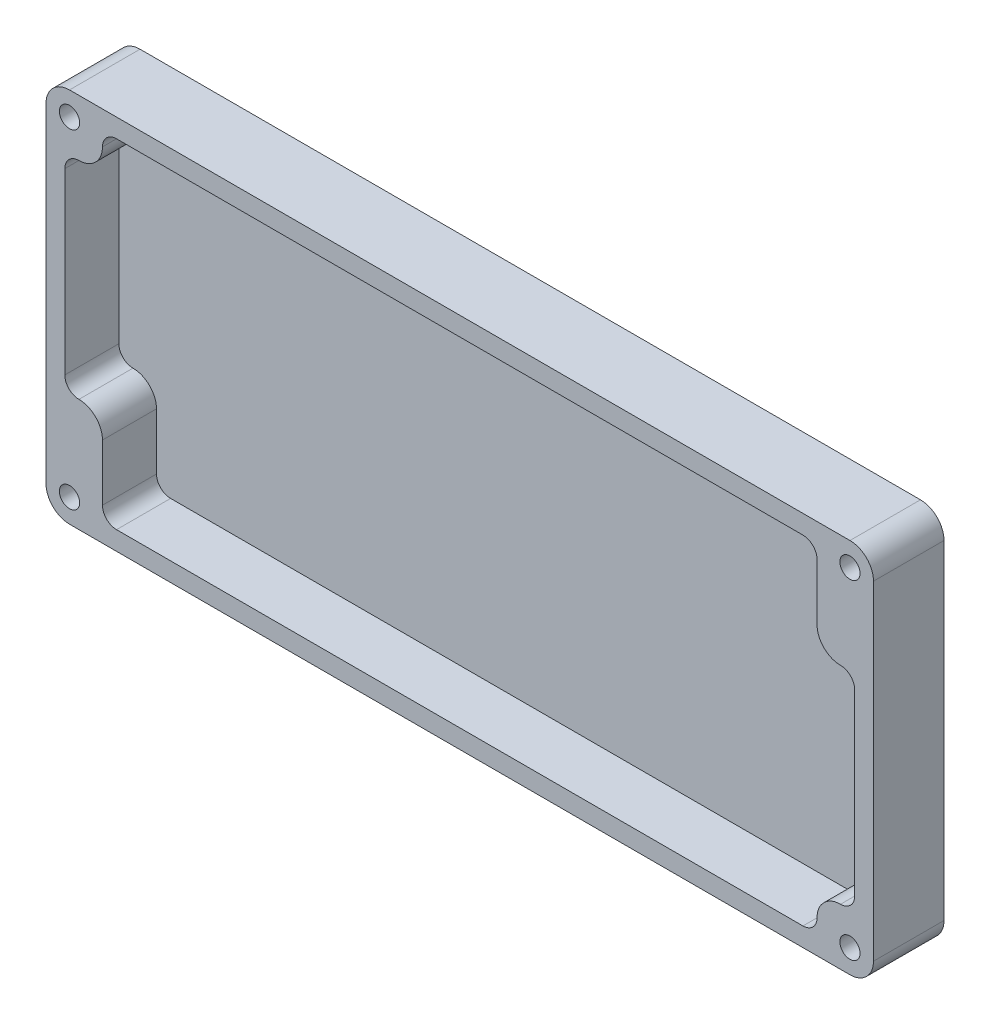
SolidWorks part; units mm, degrees
material "ألمنيوم خلائطي"
ref_plane "Front" through (0, 0, 0) normal (0, 0, 1) x (1, 0, 0)
ref_plane "Top" through (0, 0, 0) normal (0, 1, 0) x (1, 0, 0)
ref_plane "Right" through (0, 0, 0) normal (1, 0, 0) x (0, 0, -1)
sketch "Sketch1" plane through (0, 0, 0) normal (0, 0, 1) x (1, 0, 0)
  line L0 (88, 40) -> (-88, -40) construction
  line L1 (-88, 40) -> (88, 40)
  line L2 (-88, 40) -> (-88, -40)
  line L3 (-88, -40) -> (88, -40)
  line L4 (88, 40) -> (88, -40)
  dimension "D1" = 176
  dimension "D2" = 80
extrude "Boss-Extrude1" add sketch "Sketch1" along normal blind 38.5
sketch "Sketch2" plane through (0, 0, 38.5) normal (0, 0, 1) x (1, 0, 0)
  line L8 (-84, 36) -> (-84, -36)
  line L9 (-84, -36) -> (84, -36)
  line L10 (84, -36) -> (84, 36)
  line L11 (84, 36) -> (-84, 36)
  line L12 (-84, 36) -> (-84, -36)
  line L13 (-84, -36) -> (84, -36)
  line L14 (84, -36) -> (84, 36)
  line L15 (84, 36) -> (-84, 36)
  dimension "D1" = 4
extrude "Cut-Extrude1" cut sketch "Sketch2" against normal blind 35
fillet "Fillet2" radius 5 4 edges at (88, 40, 19.25) (88, -40, 19.25) (-88, -40, 19.25) (-88, 40, 19.25)
sketch "Sketch8" plane through (0, 0, 3.5) normal (0, 0, 1) x (1, 0, 0)
  line L0 (84, 36) -> (-84, 36) construction
  line L1 (76, 36) -> (84, 36)
  line L2 (76, 36) -> (76, 16)
  line L3 (76, 16) -> (84, 16)
  line L4 (84, 36) -> (84, 16)
  line L5 (84, -36) -> (84, 36) construction
  line L6 (-84, -36) -> (84, -36) construction
  line L7 (84, -28) -> (76, -28)
  line L8 (84, -28) -> (84, -36)
  line L9 (84, -36) -> (76, -36)
  line L10 (76, -28) -> (76, -36)
  line L11 (-84, 36) -> (-84, -36) construction
  line L12 (-76, -36) -> (-84, -36)
  line L13 (-76, -36) -> (-76, -16)
  line L14 (-76, -16) -> (-84, -16)
  line L15 (-84, -36) -> (-84, -16)
  line L16 (88, -35) -> (88, 35) construction
  line L17 (-84, 28) -> (-76, 28)
  line L18 (-84, 28) -> (-84, 36)
  line L19 (-84, 36) -> (-76, 36)
  line L20 (-76, 28) -> (-76, 36)
  dimension "D1" = 12
  dimension "D2" = 20
extrude "Boss-Extrude2" add sketch "Sketch8" along normal up to surface (35 mm away) up to face at (0, 0, 38.5)
fillet "Fillet4" radius 3 8 edges at (-76, 36, 21) (84, -28, 21) (76, -36, 21) (-76, -36, 21) (-84, -16, 21) (-84, 28, 21) (84, 16, 21) (76, 36, 21)
fillet "Fillet5" radius 5 4 edges at (-76, -16, 21) (76, -28, 21) (76, 16, 21) (-76, 28, 21)
hole_wizard "M4 Tapped Hole1" positions "Sketch5" profile "Sketch4" tap size "M4" standard "ISO"
sketch "Sketch5" plane through (0, 0, 38.5) normal (0, 0, 1) x (1, 0, 0)
  line L0 (-83, 35) -> (83, 35) construction
  line L1 (83, 35) -> (83, -35) construction
  line L2 (83, -35) -> (-83, -35) construction
  line L3 (-83, -35) -> (-83, 35) construction
  line L5 (-83, -35) -> (83, 35) construction
  line L7 (88, -35) -> (88, 35) construction
  line L8 (83, 40) -> (-83, 40) construction
  point P1 (-83, -35)
  point P5 (83, 35)
  point P33 (-83, 35)
  point P35 (83, -35)
  dimension "D1" = 5
  dimension "D2" = 5
sketch "Sketch4" plane through (-83, -35, 38.5) normal (1, 0, 0) x (0, -1, 0)
  line L0 (0, 0) -> (0, 12.4914)
  line L1 (0, 12.4914) -> (1.65, 11.5)
  line L2 (1.65, 11.5) -> (1.65, 0)
  line L5 (1.65, 0) -> (0, 0)
  line L10 (0, 12.4914) -> (-1.65, 11.5) construction
  line L11 (0, -6.35) -> (0, 107.95) construction
  dimension "Tap Drill Dia." = 3.3
  dimension "Tap Drill Depth" = 11.5
  dimension "Drill Angle" = 118
cosmetic thread "Hole Thread1" parameters "D1"=8, "D2"=4
cosmetic thread "Hole Thread2" parameters "D1"=8, "D2"=4
cosmetic thread "Hole Thread3" parameters "D1"=8, "D2"=4
cosmetic thread "Hole Thread4" parameters "D1"=8, "D2"=4
sketch "Sketch9" plane through (0, 0, 38.5) normal (0, 0, 1) x (1, 0, 0)
  line L0 (73, 37.5) -> (-73, 37.5)
  line L1 (-85.5, 25) -> (-85.5, -13)
  line L2 (-77.5, -21) -> (-77.5, -33)
  line L3 (-73, -37.5) -> (73, -37.5)
  line L4 (85.5, -25) -> (85.5, 13)
  line L5 (77.5, 21) -> (77.5, 33)
  line L6 (73, 36) -> (-73, 36)
  line L7 (-84, 25) -> (-84, -13)
  line L8 (-76, -21) -> (-76, -33)
  line L9 (-73, -36) -> (73, -36)
  line L10 (84, -25) -> (84, 13)
  line L11 (76, 21) -> (76, 33)
  line L12 (73, 36) -> (-73, 36)
  line L13 (-84, 25) -> (-84, -13)
  line L14 (-76, -21) -> (-76, -33)
  line L15 (-73, -36) -> (73, -36)
  line L16 (84, -25) -> (84, 13)
  line L17 (76, 21) -> (76, 33)
  arc A0 (-73, 37.5) -> (-77.5, 33) centre (-73, 33) ccw
  arc A1 (-81, 29.5) -> (-77.5, 33) centre (-81, 33) ccw
  arc A2 (-81, 29.5) -> (-85.5, 25) centre (-81, 25) ccw
  arc A3 (-85.5, -13) -> (-81, -17.5) centre (-81, -13) ccw
  arc A4 (-77.5, -21) -> (-81, -17.5) centre (-81, -21) ccw
  arc A5 (-77.5, -33) -> (-73, -37.5) centre (-73, -33) ccw
  arc A6 (73, -37.5) -> (77.5, -33) centre (73, -33) ccw
  arc A7 (81, -29.5) -> (77.5, -33) centre (81, -33) ccw
  arc A8 (81, -29.5) -> (85.5, -25) centre (81, -25) ccw
  arc A9 (85.5, 13) -> (81, 17.5) centre (81, 13) ccw
  arc A10 (77.5, 21) -> (81, 17.5) centre (81, 21) ccw
  arc A11 (77.5, 33) -> (73, 37.5) centre (73, 33) ccw
  arc A12 (-73, 36) -> (-76, 33) centre (-73, 33) ccw
  arc A13 (-81, 28) -> (-76, 33) centre (-81, 33) ccw
  arc A14 (-81, 28) -> (-84, 25) centre (-81, 25) ccw
  arc A15 (-84, -13) -> (-81, -16) centre (-81, -13) ccw
  arc A16 (-76, -21) -> (-81, -16) centre (-81, -21) ccw
  arc A17 (-76, -33) -> (-73, -36) centre (-73, -33) ccw
  arc A18 (73, -36) -> (76, -33) centre (73, -33) ccw
  arc A19 (81, -28) -> (76, -33) centre (81, -33) ccw
  arc A20 (81, -28) -> (84, -25) centre (81, -25) ccw
  arc A21 (84, 13) -> (81, 16) centre (81, 13) ccw
  arc A22 (76, 21) -> (81, 16) centre (81, 21) ccw
  arc A23 (76, 33) -> (73, 36) centre (73, 33) ccw
  arc A24 (-73, 36) -> (-76, 33) centre (-73, 33) ccw
  arc A25 (-81, 28) -> (-76, 33) centre (-81, 33) ccw
  arc A26 (-81, 28) -> (-84, 25) centre (-81, 25) ccw
  arc A27 (-84, -13) -> (-81, -16) centre (-81, -13) ccw
  arc A28 (-76, -21) -> (-81, -16) centre (-81, -21) ccw
  arc A29 (-76, -33) -> (-73, -36) centre (-73, -33) ccw
  arc A30 (73, -36) -> (76, -33) centre (73, -33) ccw
  arc A31 (81, -28) -> (76, -33) centre (81, -33) ccw
  arc A32 (81, -28) -> (84, -25) centre (81, -25) ccw
  arc A33 (84, 13) -> (81, 16) centre (81, 13) ccw
  arc A34 (76, 21) -> (81, 16) centre (81, 21) ccw
  arc A35 (76, 33) -> (73, 36) centre (73, 33) ccw
  dimension "D1" = 0
  dimension "D2" = 1.5
extrude "Boss-Extrude3" add sketch "Sketch9" along normal blind 1.5
sketch "Sketch25" plane through (0, 0, 40) normal (0, 0, 1) x (1, 0, 0)
  line L1 (-98.8113, -45.3412) -> (94.1146, -45.3412)
  line L2 (-98.8113, -45.3412) -> (-98.8113, 47.5089)
  line L3 (-98.8113, 47.5089) -> (94.1146, 47.5089)
  line L4 (94.1146, -45.3412) -> (94.1146, 47.5089)
extrude "Cut-Extrude4" cut sketch "Sketch25" against normal offset from surface (25 mm away) 15 up to face at (0, 0, 0)
hole_wizard "CBORE for M4 Cheese Head Screw2" positions "Sketch33" profile "Sketch32" counterbore size "M4" standard "ISO" end condition up to next
sketch "Sketch33" plane through (0, 0, 0) normal (0, 0, -1) x (-1, 0, 0)
  line L0 (83, 35) -> (-83, 35) construction
  line L1 (-83, 35) -> (-83, -35) construction
  line L2 (-83, -35) -> (83, -35) construction
  line L3 (83, -35) -> (83, 35) construction
  line L6 (0, 0) -> (0, 35) construction
  line L8 (0, 0) -> (-83, 0) construction
  point P0 (-83, 35)
  point P2 (83, 35)
  point P4 (83, -35)
  point P6 (-83, -35)
  dimension "D1" = 166
  dimension "D2" = 70
sketch "Sketch32" plane through (83, 35, 0) normal (1, 0, 0) x (0, 1, 0)
  line L0 (0, 0) -> (0, 15)
  line L1 (0, 15) -> (2.15, 15)
  line L3 (2.15, 15) -> (2.15, 2.6)
  line L4 (2.15, 2.6) -> (4, 2.6)
  line L5 (4, 2.6) -> (4, 0)
  line L7 (4, 0) -> (0, 0)
  line L11 (0, -6.35) -> (0, 107.95) construction
  dimension "Thru Hole Dia." = 4.3
  dimension "Thru Hole Depth" = 15
  dimension "C'Bore Dia." = 8
  dimension "C'Bore Depth" = 2.6
